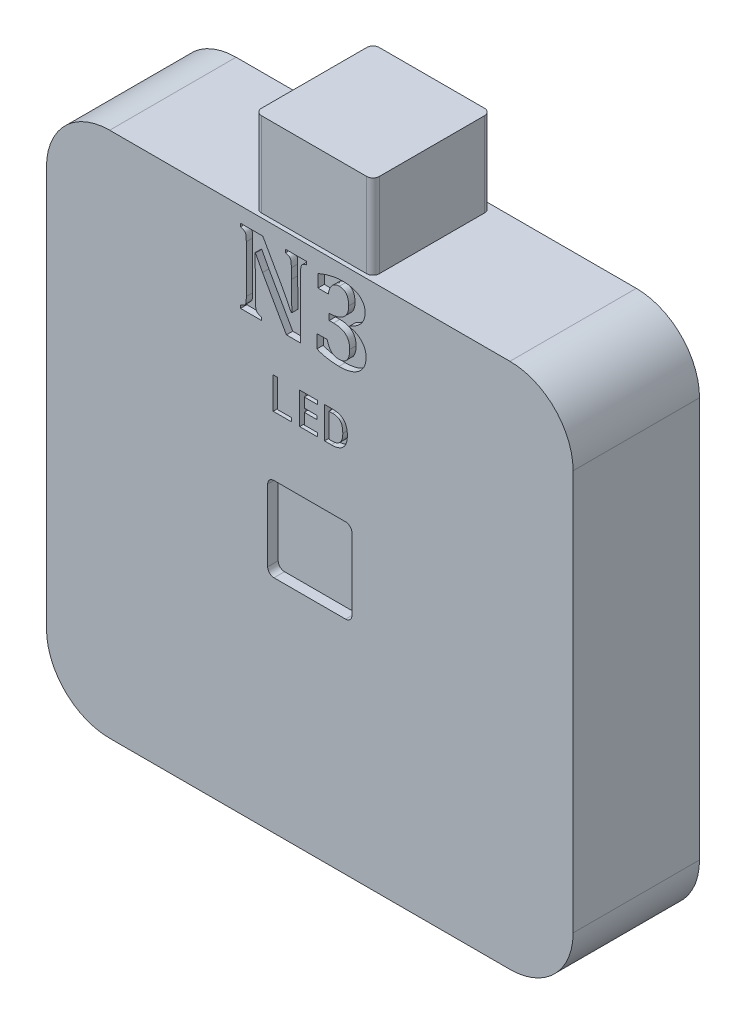
SolidWorks part; units mm, degrees
ref_plane "前视基准面" through (0, 0, 0) normal (0, 0, 1) x (1, 0, 0)
ref_plane "上视基准面" through (0, 0, 0) normal (0, 1, 0) x (1, 0, 0)
ref_plane "右视基准面" through (0, 0, 0) normal (1, 0, 0) x (0, 0, -1)
sketch "Main" plane through (0, 0, 0) normal (0, 0, 1) x (1, 0, 0)
  line L0 (-12.5, 9.5) -> (-12.5, -9.5)
  line L1 (0, 0) -> (30.1154, 0) construction
  line L2 (0, -7.3749) -> (0, 9.6594) construction
  line L3 (-9.5, 12.5) -> (9.5, 12.5)
  line L4 (12.5, 9.5) -> (12.5, -9.5)
  line L5 (-9.5, -12.5) -> (9.5, -12.5)
  arc A0 (-12.5, 9.5) -> (-9.5, 12.5) centre (-9.5, 9.5) cw
  arc A1 (12.5, 9.5) -> (9.5, 12.5) centre (9.5, 9.5) ccw
  arc A2 (12.5, -9.5) -> (9.5, -12.5) centre (9.5, -9.5) cw
  arc A3 (-12.5, -9.5) -> (-9.5, -12.5) centre (-9.5, -9.5) ccw
  point P6 (-12.5, 0)
  point P12 (0, 12.5)
  dimension "D2" = 3
  dimension "D1" = 12.5
  dimension "D4" = 12.5
extrude "Main_P" add sketch "Main" along normal mid plane 6
sketch "LED" plane through (0, 0, 3) normal (0, 0, 1) x (1, 0, 0)
  line L0 (-2, 1.7) -> (-2, -1.7)
  line L1 (0, 0) -> (0, 2.0647) construction
  line L2 (0, 0) -> (2.1929, 0) construction
  line L3 (1.7, 2) -> (-1.7, 2)
  line L4 (1.7, -2) -> (-1.7, -2)
  line L5 (2, 1.7) -> (2, -1.7)
  arc A1 (-2, 1.7) -> (-1.7, 2) centre (-1.7, 1.7) cw
  arc A2 (-1.7, -2) -> (-2, -1.7) centre (-1.7, -1.7) cw
  arc A3 (1.7, 2) -> (2, 1.7) centre (1.7, 1.7) cw
  arc A4 (1.7, -2) -> (2, -1.7) centre (1.7, -1.7) ccw
  point P14 (-2, 0)
  point P21 (0, -2)
  point P23 (0, 2)
  dimension "D4" = 0.3
  dimension "D1" = 2
  dimension "D2" = 2
extrude "LED_P" cut sketch "LED" against normal blind 0.5 contours L4 A4 L5 A3 L3 L0 A2 region at (0, 0, 3)
sketch "草图3" plane through (0, 0, 3) normal (0, 0, 1) x (1, 0, 0)
  line L0 (0, 0) -> (18.2534, 0) construction
  line L1 (0, 0) -> (0, 13.6083) construction
  text T0 "N3" font "Cambria" height 3.5
  text T1 "LED" font "Consolas" height 1.5
  dimension "D1" = 3.55
  dimension "D2" = 2
extrude "N3_LED_P" cut sketch "草图3" against normal blind 0.3
sketch "草图4" plane through (0, 12.5, 0) normal (0, 1, 0) x (1, 0, 0)
  line L1 (-2.5, 2.8) -> (2.5, 2.8)
  line L2 (-2.8, 2.5) -> (-2.8, -2.5)
  line L3 (-2.5, -2.8) -> (2.5, -2.8)
  line L4 (2.8, 2.5) -> (2.8, -2.5)
  arc A0 (-2.8, 2.5) -> (-2.5, 2.8) centre (-2.5, 2.5) cw
  arc A1 (-2.8, -2.5) -> (-2.5, -2.8) centre (-2.5, -2.5) ccw
  arc A2 (2.8, -2.5) -> (2.5, -2.8) centre (2.5, -2.5) cw
  arc A3 (2.8, 2.5) -> (2.5, 2.8) centre (2.5, 2.5) ccw
  dimension "D3" = 0.3
  dimension "D1" = 2.8
  dimension "D2" = 2.8
  dimension "D4" = 5.6
  dimension "D5" = 5.6
extrude "Cable_up_P" add sketch "草图4" along normal blind 4
sketch "草图5" plane through (0, -12.5, 0) normal (0, -1, 0) x (1, 0, 0)
  point P7 (0, -0.8)
  point P10 (0, 1.2)
  line B0 (-14.5459, 0) -> (14.5459, 0) construction
  line B1 (0, 8.6152) -> (0, -8.7884) construction
  line B2 (-3.25, -0.8) -> (3.25, -0.8)
  line B3 (-2.5, 1.2) -> (2.5, 1.2)
  line B4 (-3.25, -0.8) -> (-3.25, 0)
  line B5 (3.25, -0.8) -> (3.25, 0)
  line B6 (-2.5, 1.2) -> (-3.25, 0)
  line B7 (2.5, 1.2) -> (3.25, 0)
sketch_block_instance "块1-1"
sketch_block "块1" parameters "D1"=6.5, "D2"=5, "D3"=2, "D4"=0.8
extrude "USB_P" cut sketch "草图5" against normal blind 5
